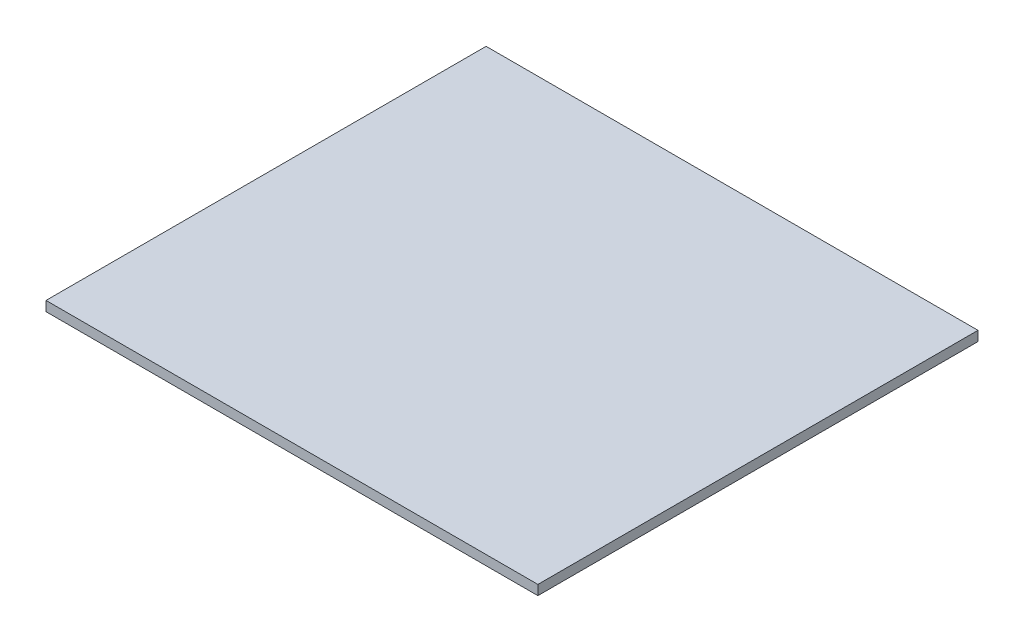
SolidWorks part; units mm, degrees
ref_plane "Front" through (0, 0, 0) normal (0, 0, 1) x (1, 0, 0)
ref_plane "Top" through (0, 0, 0) normal (0, 1, 0) x (1, 0, 0)
ref_plane "Right" through (0, 0, 0) normal (1, 0, 0) x (0, 0, -1)
sketch "Sketch1" plane through (0, 0, 0) normal (0, 1, 0) x (1, 0, 0)
  line L1 (0, 0) -> (302.4, 0)
  line L2 (0, 0) -> (0, 270.57)
  line L3 (0, 270.57) -> (302.4, 270.57)
  line L4 (302.4, 0) -> (302.4, 270.57)
  dimension "D1" = 302.4
  dimension "D2" = 270.57
extrude "Boss-Extrude1" add sketch "Sketch1" along normal blind 6
